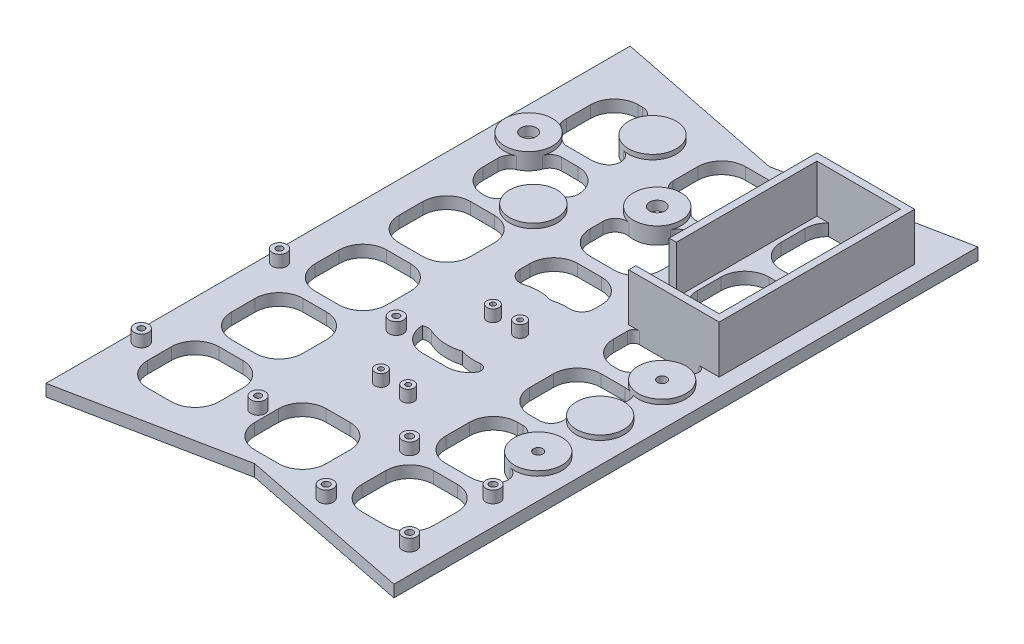
SolidWorks part; units mm, degrees
material "ABS"
ref_plane "Front Plane" through (0, 0, 0) normal (0, 0, 1) x (1, 0, 0)
ref_plane "Top Plane" through (0, 0, 0) normal (0, 1, 0) x (1, 0, 0)
ref_plane "Right Plane" through (0, 0, 0) normal (1, 0, 0) x (0, 0, -1)
ref_axis "X" through (-88.99, 0, 0) along (1, 0, 0)
ref_axis "Y" through (0, 55, 0) along (0, -1, 0)
ref_axis "Z" through (0, 0, -88.99) along (0, 0, 1)
sketch "Sketch1" plane through (0, 0, 0) normal (0, 1, 0) x (1, 0, 0)
  line L0 (-75, 125) -> (0, 110) construction
  line L1 (-75, 125) -> (75, 125) construction
  line L2 (-75, 125) -> (-75, -125) construction
  line L3 (-75, -125) -> (75, -125) construction
  line L4 (75, 125) -> (75, -125) construction
  line L5 (-75, 125) -> (75, -125) construction
  line L6 (-75, -125) -> (75, 125) construction
  line L7 (0, 110) -> (75, 125) construction
  line L8 (-75, 0) -> (75, 0) construction
  line L9 (-75, -125) -> (0, -110) construction
  line L10 (0, -110) -> (75, -125) construction
  line L11 (-73, 122.5604) -> (-73, -122.5604)
  line L12 (-73, -122.5604) -> (0, -107.9604)
  line L13 (0, -107.9604) -> (73, -122.5604)
  line L14 (73, 122.5604) -> (73, -122.5604)
  line L15 (0, 107.9604) -> (73, 122.5604)
  line L16 (-73, 122.5604) -> (0, 107.9604)
  point P0 (0, 0)
  dimension "D1" = 250
  dimension "D2" = 150
  dimension "D3" = 15
  dimension "D4" = 2
extrude "Boss-Extrude1" add sketch "Sketch1" along normal blind 2
sketch "Sketch2" plane through (0, 2, 0) normal (0, 1, 0) x (1, 0, 0)
  line L0 (-73, 122.5604) -> (-73, -122.5604) construction
  line L1 (-50, -102.9604) -> (-40, -102.9604)
  line L2 (-60, -92.9604) -> (-60, -82.9604)
  line L3 (-50, -72.9604) -> (-40, -72.9604)
  line L4 (-30, -92.9604) -> (-30, -82.9604)
  line L5 (-15, -92.9604) -> (-15, -82.9604)
  line L6 (-5, -102.9604) -> (5, -102.9604)
  line L7 (15, -92.9604) -> (15, -82.9604)
  line L8 (-5, -72.9604) -> (5, -72.9604)
  line L9 (30, -92.9604) -> (30, -82.9604)
  line L10 (40, -102.9604) -> (50, -102.9604)
  line L11 (60, -92.9604) -> (60, -82.9604)
  line L12 (40, -72.9604) -> (50, -72.9604)
  line L73 (-60, -57.7762) -> (-60, -47.7762)
  line L74 (-50, -67.7762) -> (-40, -67.7762)
  line L75 (-30, -57.7762) -> (-30, -47.7762)
  line L76 (-50, -37.7762) -> (-40, -37.7762)
  line L77 (-15, -57.7762) -> (-15, -47.7762)
  line L78 (-5, -37.7762) -> (5, -37.7762)
  line L79 (15, -57.7762) -> (15, -47.7762)
  line L80 (-5, -67.7762) -> (5, -67.7762)
  line L81 (30, -57.7762) -> (30, -47.7762)
  line L82 (40, -37.7762) -> (50, -37.7762)
  line L83 (60, -57.7762) -> (60, -47.7762)
  line L84 (40, -67.7762) -> (50, -67.7762)
  line L85 (-60, -22.5921) -> (-60, -12.5921)
  line L86 (-50, -32.5921) -> (-40, -32.5921)
  line L87 (-30, -22.5921) -> (-30, -12.5921)
  line L88 (-50, -2.5921) -> (-40, -2.5921)
  line L89 (-15, -22.5921) -> (-15, -12.5921)
  line L90 (-5, -2.5921) -> (5, -2.5921)
  line L91 (15, -22.5921) -> (15, -12.5921)
  line L92 (-5, -32.5921) -> (5, -32.5921)
  line L93 (30, -22.5921) -> (30, -12.5921)
  line L94 (40, -2.5921) -> (50, -2.5921)
  line L95 (60, -22.5921) -> (60, -12.5921)
  line L96 (40, -32.5921) -> (50, -32.5921)
  line L97 (-60, 12.5921) -> (-60, 22.5921)
  line L98 (-50, 2.5921) -> (-40, 2.5921)
  line L99 (-30, 12.5921) -> (-30, 22.5921)
  line L100 (-50, 32.5921) -> (-40, 32.5921)
  line L101 (-15, 12.5921) -> (-15, 22.5921)
  line L102 (-5, 32.5921) -> (5, 32.5921)
  line L103 (15, 12.5921) -> (15, 22.5921)
  line L104 (-5, 2.5921) -> (5, 2.5921)
  line L105 (30, 12.5921) -> (30, 22.5921)
  line L106 (40, 32.5921) -> (50, 32.5921)
  line L107 (60, 12.5921) -> (60, 22.5921)
  line L108 (40, 2.5921) -> (50, 2.5921)
  line L109 (-60, 47.7762) -> (-60, 57.7762)
  line L110 (-50, 37.7762) -> (-40, 37.7762)
  line L111 (-30, 47.7762) -> (-30, 57.7762)
  line L112 (-50, 67.7762) -> (-40, 67.7762)
  line L113 (-15, 47.7762) -> (-15, 57.7762)
  line L114 (-5, 67.7762) -> (5, 67.7762)
  line L115 (15, 47.7762) -> (15, 57.7762)
  line L116 (-5, 37.7762) -> (5, 37.7762)
  line L117 (30, 47.7762) -> (30, 57.7762)
  line L118 (40, 67.7762) -> (50, 67.7762)
  line L119 (60, 47.7762) -> (60, 57.7762)
  line L120 (40, 37.7762) -> (50, 37.7762)
  line L121 (-60, 82.9604) -> (-60, 92.9604)
  line L122 (-50, 72.9604) -> (-40, 72.9604)
  line L123 (-30, 82.9604) -> (-30, 92.9604)
  line L124 (-50, 102.9604) -> (-40, 102.9604)
  line L125 (-15, 82.9604) -> (-15, 92.9604)
  line L126 (-5, 102.9604) -> (5, 102.9604)
  line L127 (15, 82.9604) -> (15, 92.9604)
  line L128 (-5, 72.9604) -> (5, 72.9604)
  line L129 (30, 82.9604) -> (30, 92.9604)
  line L130 (40, 102.9604) -> (50, 102.9604)
  line L131 (60, 82.9604) -> (60, 92.9604)
  line L132 (40, 72.9604) -> (50, 72.9604)
  arc A0 (-60, -92.9604) -> (-50, -102.9604) centre (-50, -92.9604) ccw
  arc A1 (-40, -102.9604) -> (-30, -92.9604) centre (-40, -92.9604) ccw
  arc A2 (-30, -82.9604) -> (-40, -72.9604) centre (-40, -82.9604) ccw
  arc A3 (-50, -72.9604) -> (-60, -82.9604) centre (-50, -82.9604) ccw
  arc A4 (60, -82.9604) -> (50, -72.9604) centre (50, -82.9604) ccw
  arc A5 (50, -102.9604) -> (60, -92.9604) centre (50, -92.9604) ccw
  arc A6 (40, -102.9604) -> (30, -92.9604) centre (40, -92.9604) cw
  arc A7 (30, -82.9604) -> (40, -72.9604) centre (40, -82.9604) cw
  arc A8 (-15, -82.9604) -> (-5, -72.9604) centre (-5, -82.9604) cw
  arc A9 (-15, -92.9604) -> (-5, -102.9604) centre (-5, -92.9604) ccw
  arc A10 (15, -92.9604) -> (5, -102.9604) centre (5, -92.9604) cw
  arc A11 (15, -82.9604) -> (5, -72.9604) centre (5, -82.9604) ccw
  arc A12 (-50, -37.7762) -> (-60, -47.7762) centre (-50, -47.7762) ccw
  arc A13 (-60, -57.7762) -> (-50, -67.7762) centre (-50, -57.7762) ccw
  arc A14 (-40, -67.7762) -> (-30, -57.7762) centre (-40, -57.7762) ccw
  arc A15 (-30, -47.7762) -> (-40, -37.7762) centre (-40, -47.7762) ccw
  arc A16 (-15, -57.7762) -> (-5, -67.7762) centre (-5, -57.7762) ccw
  arc A17 (-15, -47.7762) -> (-5, -37.7762) centre (-5, -47.7762) cw
  arc A18 (15, -47.7762) -> (5, -37.7762) centre (5, -47.7762) ccw
  arc A19 (15, -57.7762) -> (5, -67.7762) centre (5, -57.7762) cw
  arc A20 (30, -47.7762) -> (40, -37.7762) centre (40, -47.7762) cw
  arc A21 (40, -67.7762) -> (30, -57.7762) centre (40, -57.7762) cw
  arc A22 (60, -47.7762) -> (50, -37.7762) centre (50, -47.7762) ccw
  arc A23 (50, -67.7762) -> (60, -57.7762) centre (50, -57.7762) ccw
  arc A24 (-50, -2.5921) -> (-60, -12.5921) centre (-50, -12.5921) ccw
  arc A25 (-60, -22.5921) -> (-50, -32.5921) centre (-50, -22.5921) ccw
  arc A26 (-40, -32.5921) -> (-30, -22.5921) centre (-40, -22.5921) ccw
  arc A27 (-30, -12.5921) -> (-40, -2.5921) centre (-40, -12.5921) ccw
  arc A28 (-15, -22.5921) -> (-5, -32.5921) centre (-5, -22.5921) ccw
  arc A29 (-15, -12.5921) -> (-5, -2.5921) centre (-5, -12.5921) cw
  arc A30 (15, -12.5921) -> (5, -2.5921) centre (5, -12.5921) ccw
  arc A31 (15, -22.5921) -> (5, -32.5921) centre (5, -22.5921) cw
  arc A32 (30, -12.5921) -> (40, -2.5921) centre (40, -12.5921) cw
  arc A33 (40, -32.5921) -> (30, -22.5921) centre (40, -22.5921) cw
  arc A34 (60, -12.5921) -> (50, -2.5921) centre (50, -12.5921) ccw
  arc A35 (50, -32.5921) -> (60, -22.5921) centre (50, -22.5921) ccw
  arc A36 (-50, 32.5921) -> (-60, 22.5921) centre (-50, 22.5921) ccw
  arc A37 (-60, 12.5921) -> (-50, 2.5921) centre (-50, 12.5921) ccw
  arc A38 (-40, 2.5921) -> (-30, 12.5921) centre (-40, 12.5921) ccw
  arc A39 (-30, 22.5921) -> (-40, 32.5921) centre (-40, 22.5921) ccw
  arc A40 (-15, 12.5921) -> (-5, 2.5921) centre (-5, 12.5921) ccw
  arc A41 (-15, 22.5921) -> (-5, 32.5921) centre (-5, 22.5921) cw
  arc A42 (15, 22.5921) -> (5, 32.5921) centre (5, 22.5921) ccw
  arc A43 (15, 12.5921) -> (5, 2.5921) centre (5, 12.5921) cw
  arc A44 (30, 22.5921) -> (40, 32.5921) centre (40, 22.5921) cw
  arc A45 (40, 2.5921) -> (30, 12.5921) centre (40, 12.5921) cw
  arc A46 (60, 22.5921) -> (50, 32.5921) centre (50, 22.5921) ccw
  arc A47 (50, 2.5921) -> (60, 12.5921) centre (50, 12.5921) ccw
  arc A48 (-50, 67.7762) -> (-60, 57.7762) centre (-50, 57.7762) ccw
  arc A49 (-60, 47.7762) -> (-50, 37.7762) centre (-50, 47.7762) ccw
  arc A50 (-40, 37.7762) -> (-30, 47.7762) centre (-40, 47.7762) ccw
  arc A51 (-30, 57.7762) -> (-40, 67.7762) centre (-40, 57.7762) ccw
  arc A52 (-15, 47.7762) -> (-5, 37.7762) centre (-5, 47.7762) ccw
  arc A53 (-15, 57.7762) -> (-5, 67.7762) centre (-5, 57.7762) cw
  arc A54 (15, 57.7762) -> (5, 67.7762) centre (5, 57.7762) ccw
  arc A55 (15, 47.7762) -> (5, 37.7762) centre (5, 47.7762) cw
  arc A56 (30, 57.7762) -> (40, 67.7762) centre (40, 57.7762) cw
  arc A57 (40, 37.7762) -> (30, 47.7762) centre (40, 47.7762) cw
  arc A58 (60, 57.7762) -> (50, 67.7762) centre (50, 57.7762) ccw
  arc A59 (50, 37.7762) -> (60, 47.7762) centre (50, 47.7762) ccw
  arc A60 (-50, 102.9604) -> (-60, 92.9604) centre (-50, 92.9604) ccw
  arc A61 (-60, 82.9604) -> (-50, 72.9604) centre (-50, 82.9604) ccw
  arc A62 (-40, 72.9604) -> (-30, 82.9604) centre (-40, 82.9604) ccw
  arc A63 (-30, 92.9604) -> (-40, 102.9604) centre (-40, 92.9604) ccw
  arc A64 (-15, 82.9604) -> (-5, 72.9604) centre (-5, 82.9604) ccw
  arc A65 (-15, 92.9604) -> (-5, 102.9604) centre (-5, 92.9604) cw
  arc A66 (15, 92.9604) -> (5, 102.9604) centre (5, 92.9604) ccw
  arc A67 (15, 82.9604) -> (5, 72.9604) centre (5, 82.9604) cw
  arc A68 (30, 92.9604) -> (40, 102.9604) centre (40, 92.9604) cw
  arc A69 (40, 72.9604) -> (30, 82.9604) centre (40, 82.9604) cw
  arc A70 (60, 92.9604) -> (50, 102.9604) centre (50, 92.9604) ccw
  arc A71 (50, 72.9604) -> (60, 82.9604) centre (50, 82.9604) ccw
  point P81 (-30, -102.9604)
  point P84 (-30, -72.9604)
  point P87 (-60, -72.9604)
  dimension "D9" = 10
  dimension "D7" = 10
  dimension "D1" = 30
  dimension "D2" = 30
  dimension "D3" = 13
  dimension "D4" = 5
  dimension "D6" = 15
  dimension "D8" = 6
  dimension "D10" = 5
  dimension "D5" = 3
extrude "Cut-Extrude1" cut sketch "Sketch2" against normal through all
sketch "Sketch3" plane through (0, 2, 0) normal (0, 1, 0) x (1, 0, 0)
  line L1 (-73, 122.5604) -> (-73, -122.5604) construction
  circle A0 centre (-68, -29.5604) radius 3
  circle A1 centre (-19, -29.5604) radius 3
  circle A2 centre (-68, -87.5604) radius 3
  circle A3 centre (-19, -87.5604) radius 3
  dimension "D1" = 6
  dimension "D2" = 49
  dimension "D3" = 58
  dimension "D4" = 5
  dimension "D5" = 35
extrude "Boss-Extrude2" add sketch "Sketch3" along normal blind 5 and the other way through all
sketch "Sketch4" plane through (0, 7, 0) normal (0, 1, 0) x (1, 0, 0)
  circle A1 centre (-19, -87.5604) radius 1.35
  circle A2 centre (-68, -87.5604) radius 1.35
  circle A3 centre (-68, -29.5604) radius 1.35
  circle A4 centre (-19, -29.5604) radius 1.35
  dimension "D1" = 2.7
extrude "Cut-Extrude2" cut sketch "Sketch4" against normal through all
sketch "Sketch5" plane through (0, 2, 0) normal (0, 1, 0) x (1, 0, 0)
  line L0 (30, -87.9604) -> (60, -87.9604) construction
  line L1 (30, -82.9604) -> (30, -92.9604) construction
  line L2 (60, -92.9604) -> (60, -82.9604) construction
  circle A0 centre (27.5, -70.4604) radius 3
  circle A2 centre (62.5, -70.4604) radius 3
  circle A4 centre (62.5, -105.4604) radius 3
  circle A6 centre (27.5, -105.4604) radius 3
  circle A9 centre (45, -87.9604) radius 24.7487 construction
  dimension "D2" = 6
  dimension "D3" = 35
  dimension "D4" = 35
extrude "Boss-Extrude3" add sketch "Sketch5" along normal blind 5
sketch "Sketch6" plane through (0, 7, 0) normal (0, 1, 0) x (1, 0, 0)
  circle A0 centre (27.5, -70.4604) radius 1.5
  circle A1 centre (62.5, -70.4604) radius 1.5
  circle A2 centre (62.5, -105.4604) radius 1.5
  circle A3 centre (27.5, -105.4604) radius 1.5
  dimension "D1" = 3
extrude "Cut-Extrude3" cut sketch "Sketch6" against normal through all
sketch "Sketch7" plane through (0, 2, 0) normal (0, 1, 0) x (1, 0, 0)
  line L0 (73, -122.5604) -> (73, 122.5604) construction
  line L3 (57, 6) -> (57, -46) construction
  circle A0 centre (57, -46) radius 10
  circle A1 centre (57, 6) radius 10
  circle A2 centre (57, -20) radius 10
  point P6 (0, 0)
  point P7 (0, 0)
  dimension "D1" = 20
  dimension "D2" = 16
  dimension "D3" = 52
  dimension "D4" = 20
extrude "Boss-Extrude4" add sketch "Sketch7" along normal blind 2 and the other way through all
sketch "Sketch8" plane through (0, 4, 0) normal (0, 1, 0) x (1, 0, 0)
  circle A0 centre (57, 6) radius 1.95
  circle A1 centre (57, -46) radius 1.95
  dimension "D1" = 3.9
extrude "Cut-Extrude4" cut sketch "Sketch8" against normal through all
sketch "Sketch9" plane through (0, 2, 0) normal (0, 1, 0) x (1, 0, 0)
  line L0 (-73, 0) -> (73, 0) construction
  line L2 (-73, 122.5604) -> (-73, -122.5604) construction
  line L3 (73, -122.5604) -> (73, 122.5604) construction
  circle A0 centre (-3, -5) radius 2.5
  circle A1 centre (-3, -52) radius 2.5
  circle A2 centre (8.4, -52) radius 2.5
  circle A3 centre (8.4, -5) radius 2.5
  dimension "D1" = 5
  dimension "D4" = 70
  dimension "D2" = 11.4
  dimension "D3" = 47
  dimension "D5" = 5
extrude "Boss-Extrude5" add sketch "Sketch9" along normal blind 5
sketch "Sketch16" plane through (0, 2, 0) normal (0, -1, 0) x (1, 0, 0)
  line L0 (-5, 32.5921) -> (5, 32.5921) construction
  line L1 (-93.8107, 28.5) -> (150.737, 28.5) construction
  line L4 (-3, 52) -> (-3, 5) construction
  circle A0 centre (8.4, 52) radius 19.4079
  circle A1 centre (-3, 52) radius 19.4079
  circle A4 centre (-3, 52) radius 2.5 construction
  circle A5 centre (-3, 5) radius 2.5 construction
  circle A6 centre (-3, 52) radius 2.5 construction
  circle A7 centre (-3, 5) radius 2.5 construction
  circle A8 centre (8.4, 5) radius 19.4079
  circle A9 centre (-3, 5) radius 19.4079
  point P20 (-3, 28.5)
  circle M3 centre (8.4, 52) radius 2.5
extrude "Boss-Extrude10" add sketch "Sketch16" along normal up to surface (2 mm away) contours A0 A1 | A0 A1 M3 | M3 | A1 A0 | A9 | A8 region at (18.1683, 2, 52) region at (2.5462, 2, 52) region at (-12.7683, 2, 52) region at (8.4, 2, 52) up to face at (57, 0, -4.05)
sketch "Sketch10" plane through (0, 7, 0) normal (0, 1, 0) x (1, 0, 0)
  circle A0 centre (8.4, -5) radius 1.05
  circle A1 centre (8.4, -52) radius 1.05
  circle A2 centre (-3, -52) radius 1.05
  circle A3 centre (-3, -5) radius 1.05
  dimension "D1" = 2.1
extrude "Cut-Extrude5" cut sketch "Sketch10" against normal through all
sketch "Sketch11" plane through (0, 2, 0) normal (0, 1, 0) x (1, 0, 0)
  line L0 (-73, 122.5604) -> (-73, -122.5604) construction
  line L1 (-34, 92.9604) -> (-34, 42.9604) construction
  line L2 (-61, 67.9604) -> (-7, 67.9604) construction
  circle A3 centre (-7, 67.9604) radius 10
  circle A4 centre (-61, 67.9604) radius 10
  circle A5 centre (-34, 92.9604) radius 10
  circle A6 centre (-34, 42.9604) radius 10
  point P11 (-34, 67.9604)
  dimension "D1" = 20
  dimension "D2" = 54
  dimension "D3" = 40
  dimension "D4" = 12
  dimension "D5" = 50
extrude "Boss-Extrude6" add sketch "Sketch11" along normal blind 2 and the other way through all
sketch "Sketch12" plane through (0, 4, 0) normal (0, 1, 0) x (1, 0, 0)
  circle A0 centre (-61, 67.9604) radius 3.25
  circle A1 centre (-7, 67.9604) radius 3.25
  dimension "D1" = 6.5
extrude "Cut-Extrude6" cut sketch "Sketch12" against normal through all
sketch "Sketch13" plane through (0, 2, 0) normal (0, 1, 0) x (1, 0, 0)
  line L0 (28, 20.9604) -> (66, 20.9604)
  line L1 (66, 20.9604) -> (66, 102.9604)
  line L2 (66, 102.9604) -> (25, 102.9604)
  line L3 (25, 102.9604) -> (25, 40.9604)
  line L4 (25, 40.9604) -> (28, 40.9604)
  line L5 (28, 40.9604) -> (28, 99.9604)
  line L6 (28, 99.9604) -> (63, 99.9604)
  line L7 (63, 99.9604) -> (63, 23.9604)
  line L8 (63, 23.9604) -> (28, 23.9604)
  line L9 (28, 23.9604) -> (28, 20.9604)
  line L10 (73, -122.5604) -> (73, 122.5604) construction
  line L11 (50, 102.9604) -> (40, 102.9604) construction
  dimension "D1" = 62
  dimension "D2" = 3
  dimension "D3" = 3
  dimension "D4" = 3
  dimension "D5" = 3
  dimension "D6" = 35
  dimension "D7" = 76
  dimension "D9" = 7
extrude "Boss-Extrude7" add sketch "Sketch13" along normal blind 20 and the other way through all
fillet "Fillet2" radius 5 20 edges at (47.5986, 1, -2.5921) (51.2064, 1, 37.8493) (56.7216, 1, 29.9961) (59.7538, 1, 10.3866) (-30, 1, -52.1255) (-12.481, 1, -76.3245) (1.6603, 1, -72.9604) (-58.4629, 1, -77.6332) (-52.5371, 1, -73.2876) (-30, 1, -83.7952) (-37, 1, -102.4998) (2.9983, 1, -67.7762) (-14.3879, 1, -61.2211) (-42.5513, 1, -37.7762) (-59.9972, 1, -58.0108) (-51.0028, 1, -67.7258) (60, 1, 55.5394) (-14.7647, 1, -10.4356) (15, 1, -13.2512) (-15, 1, 20.2534)
fillet "Fillet3" radius 2.5 6 edges at (14.9777, 1, 23.2593) (60, 1, -15.5394) (30.0941, 1, -23.9604) (59.9059, 1, -23.9604) (30, 1, -20.9604) (60, 1, -20.9604)
sketch "Sketch15" plane through (0, 0, 0) normal (0, -1, 0) x (1, 0, 0)
  line L0 (0, 107.9604) -> (73, 122.5604) construction
  line L1 (-73, 122.5604) -> (0, 107.9604) construction
  line L2 (73, 122.5604) -> (73, -122.5604) construction
  line L3 (73, -122.5604) -> (0, -107.9604) construction
  line L4 (0, -107.9604) -> (-73, -122.5604) construction
  line L5 (-73, -122.5604) -> (-73, 122.5604) construction
  line L6 (0, 107.9604) -> (73, 122.5604)
  line L7 (-73, 122.5604) -> (0, 107.9604)
  line L8 (73, 122.5604) -> (73, -122.5604)
  line L9 (73, -122.5604) -> (0, -107.9604)
  line L10 (0, -107.9604) -> (-73, -122.5604)
  line L11 (-73, -122.5604) -> (-73, 122.5604)
  line L12 (0, 104.901) -> (70, 118.901)
  line L13 (70, 118.901) -> (70, -118.901)
  line L14 (70, -118.901) -> (0, -104.901)
  line L15 (0, -104.901) -> (-70, -118.901)
  line L16 (-70, -118.901) -> (-70, 118.901)
  line L17 (-70, 118.901) -> (0, 104.901)
  dimension "D1" = 3
extrude "Boss-Extrude9" add sketch "Sketch15" along normal blind 3
sketch "Sketch17" plane through (0, 0, 0) normal (0, -1, 0) x (1, 0, 0)
  line L0 (-49.8197, -72.9604) -> (-40, -72.9604) construction
  line L1 (-60, -92.9604) -> (-60, -82.9604) construction
  line L2 (-48.1421, -102.9604) -> (-50, -102.9604) construction
  line L3 (-49.8197, -72.9604) -> (-40, -72.9604)
  line L4 (-60, -92.9604) -> (-60, -82.9604)
  line L5 (-48.1421, -102.9604) -> (-50, -102.9604)
  line L6 (4.1803, -72.9604) -> (5, -72.9604) construction
  line L7 (15, -82.9604) -> (15, -92.9604) construction
  line L8 (5, -102.9604) -> (-5, -102.9604) construction
  line L9 (-15, -92.9604) -> (-15, -82.9604) construction
  line L10 (4.1803, -72.9604) -> (5, -72.9604)
  line L11 (15, -82.9604) -> (15, -92.9604)
  line L12 (5, -102.9604) -> (-5, -102.9604)
  line L13 (-15, -92.9604) -> (-15, -82.9604)
  line L14 (60, -82.9604) -> (60, -92.9604) construction
  line L16 (30, -92.9604) -> (30, -82.9604) construction
  line L17 (40, -72.9604) -> (50, -72.9604) construction
  line L18 (60, -82.9604) -> (60, -92.9604)
  line L20 (30, -92.9604) -> (30, -82.9604)
  line L21 (40, -72.9604) -> (50, -72.9604)
  line L22 (-5, -37.7762) -> (5, -37.7762) construction
  line L23 (-15, -53.2635) -> (-15, -47.7762) construction
  line L24 (15, -47.7762) -> (15, -57.7762) construction
  line L25 (-5, -37.7762) -> (5, -37.7762)
  line L26 (-15, -53.2635) -> (-15, -47.7762)
  line L27 (15, -47.7762) -> (15, -57.7762)
  line L28 (-50, -37.7762) -> (-48.9989, -37.7762) construction
  line L29 (-40, -67.7762) -> (-46.9243, -67.7762) construction
  line L30 (-60, -54.2127) -> (-60, -47.7762) construction
  line L31 (-50, -37.7762) -> (-48.9989, -37.7762)
  line L32 (-40, -67.7762) -> (-46.9243, -67.7762)
  line L33 (-60, -54.2127) -> (-60, -47.7762)
  line L36 (60, -47.7762) -> (60, -57.7762) construction
  line L37 (50, -67.7762) -> (40, -67.7762) construction
  line L38 (30, -57.7762) -> (30, -47.7762) construction
  line L39 (40, -37.7762) -> (50, -37.7762) construction
  line L42 (60, -47.7762) -> (60, -57.7762)
  line L43 (50, -67.7762) -> (40, -67.7762)
  line L44 (30, -57.7762) -> (30, -47.7762)
  line L45 (40, -37.7762) -> (50, -37.7762)
  line L54 (-5, 32.5921) -> (5, 32.5921) construction
  line L58 (-5, 32.5921) -> (5, 32.5921)
  line L62 (-30, -12.5921) -> (-30, -22.5921) construction
  line L63 (-40, -32.5921) -> (-50, -32.5921) construction
  line L64 (-60, -22.5921) -> (-60, -12.5921) construction
  line L65 (-50, -2.5921) -> (-40, -2.5921) construction
  line L66 (15, -19.3554) -> (15, -22.5921) construction
  line L67 (-15, -22.5921) -> (-15, -18.3826) construction
  line L68 (5, -32.5921) -> (-5, -32.5921) construction
  line L69 (-30, -12.5921) -> (-30, -22.5921)
  line L70 (-40, -32.5921) -> (-50, -32.5921)
  line L71 (-60, -22.5921) -> (-60, -12.5921)
  line L72 (-50, -2.5921) -> (-40, -2.5921)
  line L73 (15, -19.3554) -> (15, -22.5921)
  line L74 (-15, -22.5921) -> (-15, -18.3826)
  line L75 (5, -32.5921) -> (-5, -32.5921)
  line L76 (-30, 22.5921) -> (-30, 12.5921) construction
  line L77 (-40, 2.5921) -> (-50, 2.5921) construction
  line L78 (-60, 12.5921) -> (-60, 22.5921) construction
  line L79 (-50, 32.5921) -> (-40, 32.5921) construction
  line L80 (-30, 22.5921) -> (-30, 12.5921)
  line L81 (-40, 2.5921) -> (-50, 2.5921)
  line L82 (-60, 12.5921) -> (-60, 22.5921)
  line L83 (-50, 32.5921) -> (-40, 32.5921)
  line L90 (-30, 57.7762) -> (-30, 47.7762) construction
  line L91 (-40, 37.7762) -> (-50, 37.7762) construction
  line L92 (-60, 47.7762) -> (-60, 57.7762) construction
  line L93 (-50, 67.7762) -> (-40, 67.7762) construction
  line L94 (-30, 57.7762) -> (-30, 47.7762)
  line L95 (-40, 37.7762) -> (-50, 37.7762)
  line L96 (-60, 47.7762) -> (-60, 57.7762)
  line L97 (-50, 67.7762) -> (-40, 67.7762)
  line L98 (-30, 92.9604) -> (-30, 82.9604) construction
  line L99 (-40, 72.9604) -> (-50, 72.9604) construction
  line L100 (-60, 82.9604) -> (-60, 92.9604) construction
  line L101 (-50, 102.9604) -> (-40, 102.9604) construction
  line L102 (-30, 92.9604) -> (-30, 82.9604)
  line L103 (-40, 72.9604) -> (-50, 72.9604)
  line L104 (-60, 82.9604) -> (-60, 92.9604)
  line L105 (-50, 102.9604) -> (-40, 102.9604)
  line L106 (40, 32.5921) -> (44.0632, 32.5921) construction
  line L107 (30, 12.5921) -> (30, 22.5921) construction
  line L108 (50, 2.5921) -> (40, 2.5921) construction
  line L109 (50, -32.5921) -> (40, -32.5921) construction
  line L110 (56.4254, -23.9604) -> (33.5746, -23.9604) construction
  line L111 (32.5, -20.9604) -> (57.5, -20.9604) construction
  line L112 (30, -18.4604) -> (30, -12.5921) construction
  line L113 (40, -2.5921) -> (42.0847, -2.5921) construction
  line L114 (40, 32.5921) -> (44.0632, 32.5921)
  line L115 (30, 12.5921) -> (30, 22.5921)
  line L116 (50, 2.5921) -> (40, 2.5921)
  line L117 (50, -32.5921) -> (40, -32.5921)
  line L118 (56.4254, -23.9604) -> (33.5746, -23.9604)
  line L119 (32.5, -20.9604) -> (57.5, -20.9604)
  line L120 (30, -18.4604) -> (30, -12.5921)
  line L121 (40, -2.5921) -> (42.0847, -2.5921)
  line L122 (15, 92.9604) -> (15, 82.9604) construction
  line L123 (-5, 102.9604) -> (5, 102.9604) construction
  line L124 (-15, 82.9604) -> (-15, 92.9604) construction
  line L125 (5, 72.9604) -> (-5, 72.9604) construction
  line L126 (60, 92.9604) -> (60, 82.9604) construction
  line L127 (50, 72.9604) -> (40, 72.9604) construction
  line L128 (30, 82.9604) -> (30, 92.9604) construction
  line L129 (40, 102.9604) -> (50, 102.9604) construction
  line L130 (30, 47.7762) -> (30, 57.7762) construction
  line L131 (42.3505, 37.7762) -> (40, 37.7762) construction
  line L132 (40, 67.7762) -> (50, 67.7762) construction
  line L133 (15, 92.9604) -> (15, 82.9604)
  line L134 (-5, 102.9604) -> (5, 102.9604)
  line L135 (-15, 82.9604) -> (-15, 92.9604)
  line L136 (5, 72.9604) -> (-5, 72.9604)
  line L137 (60, 92.9604) -> (60, 82.9604)
  line L138 (50, 72.9604) -> (40, 72.9604)
  line L139 (30, 82.9604) -> (30, 92.9604)
  line L140 (40, 102.9604) -> (50, 102.9604)
  line L141 (30, 47.7762) -> (30, 57.7762)
  line L142 (42.3505, 37.7762) -> (40, 37.7762)
  line L143 (40, 67.7762) -> (50, 67.7762)
  line L144 (32.8586, -99.9604) -> (57.1414, -99.9604) construction
  line L145 (32.8586, -99.9604) -> (57.1414, -99.9604)
  line L146 (4.1803, -70.9604) -> (5, -70.9604)
  line L147 (17, -82.9604) -> (17, -92.9604)
  line L148 (5, -104.9604) -> (-5, -104.9604)
  line L149 (-17, -92.9604) -> (-17, -82.9604)
  line L150 (62, -82.9604) -> (62, -92.9604)
  line L151 (40, -70.9604) -> (50, -70.9604)
  line L152 (28, -92.9604) -> (28, -82.9604)
  line L153 (32.0627, -101.9604) -> (57.9373, -101.9604)
  line L154 (40, -35.7762) -> (50, -35.7762)
  line L155 (28, -57.7762) -> (28, -47.7762)
  line L156 (50, -69.7762) -> (40, -69.7762)
  line L157 (62, -47.7762) -> (62, -57.7762)
  line L158 (-5, -35.7762) -> (5, -35.7762)
  line L159 (-17, -53.2635) -> (-17, -47.7762)
  line L160 (17, -47.7762) -> (17, -57.7762)
  line L161 (-50, -35.7762) -> (-48.9989, -35.7762)
  line L162 (-40, -69.7762) -> (-46.9243, -69.7762)
  line L163 (-62, -54.2127) -> (-62, -47.7762)
  line L164 (-49.8197, -70.9604) -> (-40, -70.9604)
  line L165 (-62, -92.9604) -> (-62, -82.9604)
  line L166 (-48.1421, -104.9604) -> (-50, -104.9604)
  line L167 (40, -0.5921) -> (42.0847, -0.5921)
  line L168 (28, -18.4604) -> (28, -12.5921)
  line L171 (50, -34.5921) -> (40, -34.5921)
  line L172 (-17, -22.5921) -> (-17, -18.3826)
  line L173 (5, -34.5921) -> (-5, -34.5921)
  line L174 (17, -19.3554) -> (17, -22.5921)
  line L175 (-50, -0.5921) -> (-40, -0.5921)
  line L176 (-62, -22.5921) -> (-62, -12.5921)
  line L177 (-40, -34.5921) -> (-50, -34.5921)
  line L178 (-28, -12.5921) -> (-28, -22.5921)
  line L179 (-50, 34.5921) -> (-40, 34.5921)
  line L180 (-62, 12.5921) -> (-62, 22.5921)
  line L181 (-40, 0.5921) -> (-50, 0.5921)
  line L182 (-28, 22.5921) -> (-28, 12.5921)
  line L183 (40, 34.5921) -> (44.0632, 34.5921)
  line L184 (28, 12.5921) -> (28, 22.5921)
  line L185 (50, 0.5921) -> (40, 0.5921)
  line L186 (-5, 34.5921) -> (5, 34.5921)
  line L187 (32.5, -22.9604) -> (57.5, -22.9604) construction
  line L188 (56.4254, -21.9604) -> (33.5746, -21.9604) construction
  line L189 (17, 92.9604) -> (17, 82.9604)
  line L190 (5, 70.9604) -> (-5, 70.9604)
  line L191 (-17, 82.9604) -> (-17, 92.9604)
  line L192 (-5, 104.9604) -> (5, 104.9604)
  line L193 (-50, 104.9604) -> (-40, 104.9604)
  line L194 (-62, 82.9604) -> (-62, 92.9604)
  line L195 (-40, 70.9604) -> (-50, 70.9604)
  line L196 (-28, 92.9604) -> (-28, 82.9604)
  line L197 (-50, 69.7762) -> (-40, 69.7762)
  line L198 (-62, 47.7762) -> (-62, 57.7762)
  line L199 (-40, 35.7762) -> (-50, 35.7762)
  line L200 (-28, 57.7762) -> (-28, 47.7762)
  line L201 (28, 47.7762) -> (28, 57.7762)
  line L202 (40, 69.7762) -> (50, 69.7762)
  line L203 (42.3505, 35.7762) -> (40, 35.7762)
  line L204 (62, 92.9604) -> (62, 82.9604)
  line L205 (50, 70.9604) -> (40, 70.9604)
  line L206 (28, 82.9604) -> (28, 92.9604)
  line L207 (40, 104.9604) -> (50, 104.9604)
  arc A0 (-48.1421, -102.9604) -> (-43.4281, -96.2937) centre (-48.1421, -97.9604) ccw construction
  arc A1 (-36.5518, -83.2914) -> (-43.4281, -96.2937) centre (-34, -92.9604) ccw construction
  arc A2 (-36.5518, -83.2914) -> (-35.6553, -73.9535) centre (-37.8276, -78.457) ccw construction
  arc A3 (-35.6553, -73.9535) -> (-40, -72.9604) centre (-40, -82.9604) ccw construction
  arc A4 (-49.8197, -72.9604) -> (-53.5464, -74.6271) centre (-49.8197, -77.9604) ccw construction
  arc A5 (-56.8794, -77.072) -> (-53.5464, -74.6271) centre (-61, -67.9604) ccw construction
  arc A6 (-56.8794, -77.072) -> (-59.6383, -80.2951) centre (-54.8191, -81.6278) ccw construction
  arc A7 (-59.6383, -80.2951) -> (-60, -82.9604) centre (-50, -82.9604) ccw construction
  arc A8 (-60, -92.9604) -> (-50, -102.9604) centre (-50, -92.9604) ccw construction
  arc A9 (-48.1421, -102.9604) -> (-43.4281, -96.2937) centre (-48.1421, -97.9604) ccw
  arc A10 (-36.5518, -83.2914) -> (-43.4281, -96.2937) centre (-34, -92.9604) ccw
  arc A11 (-36.5518, -83.2914) -> (-35.6553, -73.9535) centre (-37.8276, -78.457) ccw
  arc A12 (-35.6553, -73.9535) -> (-40, -72.9604) centre (-40, -82.9604) ccw
  arc A13 (-49.8197, -72.9604) -> (-53.5464, -74.6271) centre (-49.8197, -77.9604) ccw
  arc A14 (-56.8794, -77.072) -> (-53.5464, -74.6271) centre (-61, -67.9604) ccw
  arc A15 (-56.8794, -77.072) -> (-59.6383, -80.2951) centre (-54.8191, -81.6278) ccw
  arc A16 (-59.6383, -80.2951) -> (-60, -82.9604) centre (-50, -82.9604) ccw
  arc A17 (-60, -92.9604) -> (-50, -102.9604) centre (-50, -92.9604) ccw
  arc A18 (-8.9939, -77.7596) -> (0.4536, -74.6271) centre (-7, -67.9604) ccw construction
  arc A19 (4.1803, -72.9604) -> (0.4536, -74.6271) centre (4.1803, -77.9604) ccw construction
  arc A20 (15, -82.9604) -> (5, -72.9604) centre (5, -82.9604) ccw construction
  arc A21 (5, -102.9604) -> (15, -92.9604) centre (5, -92.9604) ccw construction
  arc A22 (-15, -92.9604) -> (-5, -102.9604) centre (-5, -92.9604) ccw construction
  arc A23 (-14.9818, -82.358) -> (-15, -82.9604) centre (-5, -82.9604) ccw construction
  arc A24 (-8.9939, -77.7596) -> (-14.9818, -82.358) centre (-9.9909, -82.6592) ccw construction
  arc A25 (-8.9939, -77.7596) -> (0.4536, -74.6271) centre (-7, -67.9604) ccw
  arc A26 (4.1803, -72.9604) -> (0.4536, -74.6271) centre (4.1803, -77.9604) ccw
  arc A27 (15, -82.9604) -> (5, -72.9604) centre (5, -82.9604) ccw
  arc A28 (5, -102.9604) -> (15, -92.9604) centre (5, -92.9604) ccw
  arc A29 (-15, -92.9604) -> (-5, -102.9604) centre (-5, -92.9604) ccw
  arc A30 (-14.9818, -82.358) -> (-15, -82.9604) centre (-5, -82.9604) ccw
  arc A31 (-8.9939, -77.7596) -> (-14.9818, -82.358) centre (-9.9909, -82.6592) ccw
  arc A32 (60, -82.9604) -> (50, -72.9604) centre (50, -82.9604) ccw construction
  arc A33 (57.1414, -99.9604) -> (60, -92.9604) centre (50, -92.9604) ccw construction
  arc A34 (30, -92.9604) -> (32.8586, -99.9604) centre (40, -92.9604) ccw construction
  arc A35 (40, -72.9604) -> (30, -82.9604) centre (40, -82.9604) ccw construction
  arc A36 (60, -82.9604) -> (50, -72.9604) centre (50, -82.9604) ccw
  arc A37 (57.1414, -99.9604) -> (60, -92.9604) centre (50, -92.9604) ccw
  arc A38 (30, -92.9604) -> (32.8586, -99.9604) centre (40, -92.9604) ccw
  arc A39 (40, -72.9604) -> (30, -82.9604) centre (40, -82.9604) ccw
  arc A40 (15, -47.7762) -> (5, -37.7762) centre (5, -47.7762) ccw construction
  arc A41 (-5, -37.7762) -> (-15, -47.7762) centre (-5, -47.7762) ccw construction
  arc A42 (-15, -53.2635) -> (-9, -58.1624) centre (-10, -53.2635) ccw construction
  arc A43 (8.8546, -67.0035) -> (15, -57.7762) centre (5, -57.7762) ccw construction
  arc A44 (2.2849, -64.2467) -> (8.8546, -67.0035) centre (6.9273, -62.3899) ccw construction
  arc A45 (2.2849, -64.2467) -> (-9, -58.1624) centre (-7, -67.9604) ccw construction
  arc A46 (15, -47.7762) -> (5, -37.7762) centre (5, -47.7762) ccw
  arc A47 (-5, -37.7762) -> (-15, -47.7762) centre (-5, -47.7762) ccw
  arc A48 (-15, -53.2635) -> (-9, -58.1624) centre (-10, -53.2635) ccw
  arc A49 (8.8546, -67.0035) -> (15, -57.7762) centre (5, -57.7762) ccw
  arc A50 (2.2849, -64.2467) -> (8.8546, -67.0035) centre (6.9273, -62.3899) ccw
  arc A51 (2.2849, -64.2467) -> (-9, -58.1624) centre (-7, -67.9604) ccw
  arc A52 (-50, -37.7762) -> (-60, -47.7762) centre (-50, -47.7762) ccw construction
  arc A53 (-43.9992, -42.8376) -> (-48.9989, -37.7762) centre (-48.9989, -42.7762) ccw construction
  arc A54 (-43.9992, -42.8376) -> (-34.6682, -52.938) centre (-34, -42.9604) ccw construction
  arc A55 (-30.0045, -58.0775) -> (-34.6682, -52.938) centre (-35.0023, -57.9269) ccw construction
  arc A56 (-40, -67.7762) -> (-30.0045, -58.0775) centre (-40, -57.7762) ccw construction
  arc A57 (-51.6162, -64.5043) -> (-46.9243, -67.7762) centre (-46.9243, -62.7762) ccw construction
  arc A58 (-51.6162, -64.5043) -> (-57, -58.7952) centre (-61, -67.9604) ccw construction
  arc A59 (-60, -54.2127) -> (-57, -58.7952) centre (-55, -54.2127) ccw construction
  arc A60 (-50, -37.7762) -> (-60, -47.7762) centre (-50, -47.7762) ccw
  arc A61 (-43.9992, -42.8376) -> (-48.9989, -37.7762) centre (-48.9989, -42.7762) ccw
  arc A62 (-43.9992, -42.8376) -> (-34.6682, -52.938) centre (-34, -42.9604) ccw
  arc A63 (-30.0045, -58.0775) -> (-34.6682, -52.938) centre (-35.0023, -57.9269) ccw
  arc A64 (-40, -67.7762) -> (-30.0045, -58.0775) centre (-40, -57.7762) ccw
  arc A65 (-51.6162, -64.5043) -> (-46.9243, -67.7762) centre (-46.9243, -62.7762) ccw
  arc A66 (-51.6162, -64.5043) -> (-57, -58.7952) centre (-61, -67.9604) ccw
  arc A67 (-60, -54.2127) -> (-57, -58.7952) centre (-55, -54.2127) ccw
  arc A72 (60, -47.7762) -> (50, -37.7762) centre (50, -47.7762) ccw construction
  arc A73 (50, -67.7762) -> (60, -57.7762) centre (50, -57.7762) ccw construction
  arc A74 (30, -57.7762) -> (40, -67.7762) centre (40, -57.7762) ccw construction
  arc A75 (40, -37.7762) -> (30, -47.7762) centre (40, -47.7762) ccw construction
  arc A80 (60, -47.7762) -> (50, -37.7762) centre (50, -47.7762) ccw
  arc A81 (50, -67.7762) -> (60, -57.7762) centre (50, -57.7762) ccw
  arc A82 (30, -57.7762) -> (40, -67.7762) centre (40, -57.7762) ccw
  arc A83 (40, -37.7762) -> (30, -47.7762) centre (40, -47.7762) ccw
  arc A96 (10.9351, 24.2416) -> (13.3489, 28.0963) centre (11.2617, 26.7202) ccw construction
  arc A97 (13.3489, 28.0963) -> (5, 32.5921) centre (5, 22.5921) ccw construction
  arc A98 (-5, 32.5921) -> (-15, 22.5921) centre (-5, 22.5921) ccw construction
  arc A99 (-15, 22.5921) -> (-11.0339, 22.667) centre (-13.1037, 27.2185) ccw construction
  arc A100 (10.9351, 24.2416) -> (2.7, 23.552) centre (8.4, 5) ccw construction
  arc A101 (2.7, 23.552) -> (-11.0339, 22.667) centre (-3, 5) ccw construction
  arc A107 (10.9351, 24.2416) -> (13.3489, 28.0963) centre (11.2617, 26.7202) ccw
  arc A108 (13.3489, 28.0963) -> (5, 32.5921) centre (5, 22.5921) ccw
  arc A109 (-5, 32.5921) -> (-15, 22.5921) centre (-5, 22.5921) ccw
  arc A110 (-15, 22.5921) -> (-11.0339, 22.667) centre (-13.1037, 27.2185) ccw
  arc A111 (10.9351, 24.2416) -> (2.7, 23.552) centre (8.4, 5) ccw
  arc A112 (2.7, 23.552) -> (-11.0339, 22.667) centre (-3, 5) ccw
  arc A118 (-30, -12.5921) -> (-40, -2.5921) centre (-40, -12.5921) ccw construction
  arc A119 (-40, -32.5921) -> (-30, -22.5921) centre (-40, -22.5921) ccw construction
  arc A120 (-60, -22.5921) -> (-50, -32.5921) centre (-50, -22.5921) ccw construction
  arc A121 (-50, -2.5921) -> (-60, -12.5921) centre (-50, -12.5921) ccw construction
  arc A122 (15, -19.3554) -> (9.6722, -14.3662) centre (10, -19.3554) ccw construction
  arc A123 (5, -32.5921) -> (15, -22.5921) centre (5, -22.5921) ccw construction
  arc A124 (-15, -22.5921) -> (-5, -32.5921) centre (-5, -22.5921) ccw construction
  arc A125 (-8.566, -13.5926) -> (-15, -18.3826) centre (-10, -18.3826) ccw construction
  arc A126 (2.7, -13.552) -> (9.6722, -14.3662) centre (8.4, 5) ccw construction
  arc A127 (-8.566, -13.5926) -> (2.7, -13.552) centre (-3, 5) ccw construction
  arc A128 (-30, -12.5921) -> (-40, -2.5921) centre (-40, -12.5921) ccw
  arc A129 (-40, -32.5921) -> (-30, -22.5921) centre (-40, -22.5921) ccw
  arc A130 (-60, -22.5921) -> (-50, -32.5921) centre (-50, -22.5921) ccw
  arc A131 (-50, -2.5921) -> (-60, -12.5921) centre (-50, -12.5921) ccw
  arc A132 (15, -19.3554) -> (9.6722, -14.3662) centre (10, -19.3554) ccw
  arc A133 (5, -32.5921) -> (15, -22.5921) centre (5, -22.5921) ccw
  arc A134 (-15, -22.5921) -> (-5, -32.5921) centre (-5, -22.5921) ccw
  arc A135 (-8.566, -13.5926) -> (-15, -18.3826) centre (-10, -18.3826) ccw
  arc A136 (2.7, -13.552) -> (9.6722, -14.3662) centre (8.4, 5) ccw
  arc A137 (-8.566, -13.5926) -> (2.7, -13.552) centre (-3, 5) ccw
  arc A138 (-30, 22.5921) -> (-40, 32.5921) centre (-40, 22.5921) ccw construction
  arc A139 (-40, 2.5921) -> (-30, 12.5921) centre (-40, 12.5921) ccw construction
  arc A140 (-60, 12.5921) -> (-50, 2.5921) centre (-50, 12.5921) ccw construction
  arc A141 (-50, 32.5921) -> (-60, 22.5921) centre (-50, 22.5921) ccw construction
  arc A142 (-30, 22.5921) -> (-40, 32.5921) centre (-40, 22.5921) ccw
  arc A143 (-40, 2.5921) -> (-30, 12.5921) centre (-40, 12.5921) ccw
  arc A144 (-60, 12.5921) -> (-50, 2.5921) centre (-50, 12.5921) ccw
  arc A145 (-50, 32.5921) -> (-60, 22.5921) centre (-50, 22.5921) ccw
  arc A158 (-30, 57.7762) -> (-40, 67.7762) centre (-40, 57.7762) ccw construction
  arc A159 (-40, 37.7762) -> (-30, 47.7762) centre (-40, 47.7762) ccw construction
  arc A160 (-60, 47.7762) -> (-50, 37.7762) centre (-50, 47.7762) ccw construction
  arc A161 (-50, 67.7762) -> (-60, 57.7762) centre (-50, 57.7762) ccw construction
  arc A162 (-30, 57.7762) -> (-40, 67.7762) centre (-40, 57.7762) ccw
  arc A163 (-40, 37.7762) -> (-30, 47.7762) centre (-40, 47.7762) ccw
  arc A164 (-60, 47.7762) -> (-50, 37.7762) centre (-50, 47.7762) ccw
  arc A165 (-50, 67.7762) -> (-60, 57.7762) centre (-50, 57.7762) ccw
  arc A166 (-30, 92.9604) -> (-40, 102.9604) centre (-40, 92.9604) ccw construction
  arc A167 (-40, 72.9604) -> (-30, 82.9604) centre (-40, 82.9604) ccw construction
  arc A168 (-60, 82.9604) -> (-50, 72.9604) centre (-50, 82.9604) ccw construction
  arc A169 (-50, 102.9604) -> (-60, 92.9604) centre (-50, 92.9604) ccw construction
  arc A170 (-30, 92.9604) -> (-40, 102.9604) centre (-40, 92.9604) ccw
  arc A171 (-40, 72.9604) -> (-30, 82.9604) centre (-40, 82.9604) ccw
  arc A172 (-60, 82.9604) -> (-50, 72.9604) centre (-50, 82.9604) ccw
  arc A173 (-50, 102.9604) -> (-60, 92.9604) centre (-50, 92.9604) ccw
  arc A174 (48.3755, 25.0614) -> (44.0632, 32.5921) centre (44.0632, 27.5921) ccw construction
  arc A175 (40, 32.5921) -> (30, 22.5921) centre (40, 22.5921) ccw construction
  arc A176 (30, 12.5921) -> (40, 2.5921) centre (40, 12.5921) ccw construction
  arc A177 (48.3755, 25.0614) -> (52.6284, 11.0062) centre (57, 20) ccw construction
  arc A178 (54.5808, 3.703) -> (52.6284, 11.0062) centre (50.4426, 6.5093) ccw construction
  arc A179 (50, 2.5921) -> (52.4192, 2.8891) centre (50, 12.5921) ccw construction
  arc A180 (54.5808, 3.703) -> (52.4192, 2.8891) centre (57, -6) ccw construction
  arc A181 (50, -32.5921) -> (58.5672, -27.7498) centre (50, -22.5921) ccw construction
  arc A182 (31.4328, -27.7498) -> (40, -32.5921) centre (40, -22.5921) ccw construction
  arc A183 (33.5746, -23.9604) -> (31.4328, -27.7498) centre (33.5746, -26.4604) ccw construction
  arc A184 (58.5672, -27.7498) -> (56.4254, -23.9604) centre (56.4254, -26.4604) ccw construction
  arc A185 (60, -18.4752) -> (57.4, -15.992) centre (57.5, -18.49) ccw construction
  arc A186 (57.5, -20.9604) -> (60, -18.4752) centre (57.5, -18.4604) ccw construction
  arc A187 (30, -18.4604) -> (32.5, -20.9604) centre (32.5, -18.4604) ccw construction
  arc A188 (40, -2.5921) -> (30, -12.5921) centre (40, -12.5921) ccw construction
  arc A189 (47.0565, -7.0614) -> (42.0847, -2.5921) centre (42.0847, -7.5921) ccw construction
  arc A190 (47.0565, -7.0614) -> (57.4, -15.992) centre (57, -6) ccw construction
  arc A191 (48.3755, 25.0614) -> (44.0632, 32.5921) centre (44.0632, 27.5921) ccw
  arc A192 (40, 32.5921) -> (30, 22.5921) centre (40, 22.5921) ccw
  arc A193 (30, 12.5921) -> (40, 2.5921) centre (40, 12.5921) ccw
  arc A194 (48.3755, 25.0614) -> (52.6284, 11.0062) centre (57, 20) ccw
  arc A195 (54.5808, 3.703) -> (52.6284, 11.0062) centre (50.4426, 6.5093) ccw
  arc A196 (50, 2.5921) -> (52.4192, 2.8891) centre (50, 12.5921) ccw
  arc A197 (54.5808, 3.703) -> (52.4192, 2.8891) centre (57, -6) ccw
  arc A198 (50, -32.5921) -> (58.5672, -27.7498) centre (50, -22.5921) ccw
  arc A199 (31.4328, -27.7498) -> (40, -32.5921) centre (40, -22.5921) ccw
  arc A200 (33.5746, -23.9604) -> (31.4328, -27.7498) centre (33.5746, -26.4604) ccw
  arc A201 (58.5672, -27.7498) -> (56.4254, -23.9604) centre (56.4254, -26.4604) ccw
  arc A202 (60, -18.4752) -> (57.4, -15.992) centre (57.5, -18.49) ccw
  arc A203 (57.5, -20.9604) -> (60, -18.4752) centre (57.5, -18.4604) ccw
  arc A204 (30, -18.4604) -> (32.5, -20.9604) centre (32.5, -18.4604) ccw
  arc A205 (40, -2.5921) -> (30, -12.5921) centre (40, -12.5921) ccw
  arc A206 (47.0565, -7.0614) -> (42.0847, -2.5921) centre (42.0847, -7.5921) ccw
  arc A207 (47.0565, -7.0614) -> (57.4, -15.992) centre (57, -6) ccw
  arc A208 (15, 92.9604) -> (5, 102.9604) centre (5, 92.9604) ccw construction
  arc A209 (-5, 102.9604) -> (-15, 92.9604) centre (-5, 92.9604) ccw construction
  arc A210 (-15, 82.9604) -> (-5, 72.9604) centre (-5, 82.9604) ccw construction
  arc A211 (5, 72.9604) -> (15, 82.9604) centre (5, 82.9604) ccw construction
  arc A212 (50, 72.9604) -> (60, 82.9604) centre (50, 82.9604) ccw construction
  arc A213 (30, 82.9604) -> (40, 72.9604) centre (40, 82.9604) ccw construction
  arc A214 (40, 102.9604) -> (30, 92.9604) centre (40, 92.9604) ccw construction
  arc A215 (60, 92.9604) -> (50, 102.9604) centre (50, 92.9604) ccw construction
  arc A216 (40, 67.7762) -> (30, 57.7762) centre (40, 57.7762) ccw construction
  arc A217 (30, 47.7762) -> (40, 37.7762) centre (40, 47.7762) ccw construction
  arc A218 (42.3505, 37.7762) -> (47.2337, 43.8508) centre (42.3505, 42.7762) ccw construction
  arc A219 (55.0339, 55.8048) -> (47.2337, 43.8508) centre (57, 46) ccw construction
  arc A220 (55.0339, 55.8048) -> (58.1017, 63.6382) centre (54.0508, 60.7072) ccw construction
  arc A221 (58.1017, 63.6382) -> (50, 67.7762) centre (50, 57.7762) ccw construction
  arc A222 (15, 92.9604) -> (5, 102.9604) centre (5, 92.9604) ccw
  arc A223 (-5, 102.9604) -> (-15, 92.9604) centre (-5, 92.9604) ccw
  arc A224 (-15, 82.9604) -> (-5, 72.9604) centre (-5, 82.9604) ccw
  arc A225 (5, 72.9604) -> (15, 82.9604) centre (5, 82.9604) ccw
  arc A226 (50, 72.9604) -> (60, 82.9604) centre (50, 82.9604) ccw
  arc A227 (30, 82.9604) -> (40, 72.9604) centre (40, 82.9604) ccw
  arc A228 (40, 102.9604) -> (30, 92.9604) centre (40, 92.9604) ccw
  arc A229 (60, 92.9604) -> (50, 102.9604) centre (50, 92.9604) ccw
  arc A230 (40, 67.7762) -> (30, 57.7762) centre (40, 57.7762) ccw
  arc A231 (30, 47.7762) -> (40, 37.7762) centre (40, 47.7762) ccw
  arc A232 (42.3505, 37.7762) -> (47.2337, 43.8508) centre (42.3505, 42.7762) ccw
  arc A233 (55.0339, 55.8048) -> (47.2337, 43.8508) centre (57, 46) ccw
  arc A234 (55.0339, 55.8048) -> (58.1017, 63.6382) centre (54.0508, 60.7072) ccw
  arc A235 (58.1017, 63.6382) -> (50, 67.7762) centre (50, 57.7762) ccw
  arc A236 (-8.5952, -75.7997) -> (-1.0372, -73.2937) centre (-7, -67.9604) ccw
  arc A237 (4.1803, -70.9604) -> (-1.0372, -73.2937) centre (4.1803, -77.9604) ccw
  arc A238 (17, -82.9604) -> (5, -70.9604) centre (5, -82.9604) ccw
  arc A239 (5, -104.9604) -> (17, -92.9604) centre (5, -92.9604) ccw
  arc A240 (-17, -92.9604) -> (-5, -104.9604) centre (-5, -92.9604) ccw
  arc A241 (-16.9782, -82.2375) -> (-17, -82.9604) centre (-5, -82.9604) ccw
  arc A242 (-8.5952, -75.7997) -> (-16.9782, -82.2375) centre (-9.9909, -82.6592) ccw
  arc A243 (57.9373, -101.9604) -> (62, -92.9604) centre (50, -92.9604) ccw
  arc A244 (62, -82.9604) -> (50, -70.9604) centre (50, -82.9604) ccw
  arc A245 (40, -70.9604) -> (28, -82.9604) centre (40, -82.9604) ccw
  arc A246 (28, -92.9604) -> (32.0627, -101.9604) centre (40, -92.9604) ccw
  arc A247 (62, -47.7762) -> (50, -35.7762) centre (50, -47.7762) ccw
  arc A248 (40, -35.7762) -> (28, -47.7762) centre (40, -47.7762) ccw
  arc A249 (28, -57.7762) -> (40, -69.7762) centre (40, -57.7762) ccw
  arc A250 (50, -69.7762) -> (62, -57.7762) centre (50, -57.7762) ccw
  arc A251 (17, -47.7762) -> (5, -35.7762) centre (5, -47.7762) ccw
  arc A252 (-5, -35.7762) -> (-17, -47.7762) centre (-5, -47.7762) ccw
  arc A253 (-17, -53.2635) -> (-8.6, -60.122) centre (-10, -53.2635) ccw
  arc A254 (0.4279, -64.9894) -> (-8.6, -60.122) centre (-7, -67.9604) ccw
  arc A255 (0.4279, -64.9894) -> (9.6255, -68.8489) centre (6.9273, -62.3899) ccw
  arc A256 (9.6255, -68.8489) -> (17, -57.7762) centre (5, -57.7762) ccw
  arc A257 (-41.9994, -42.8622) -> (-48.9989, -35.7762) centre (-48.9989, -42.7762) ccw
  arc A258 (-41.9994, -42.8622) -> (-34.5345, -50.9425) centre (-34, -42.9604) ccw
  arc A259 (-28.0054, -58.1378) -> (-34.5345, -50.9425) centre (-35.0023, -57.9269) ccw
  arc A260 (-40, -69.7762) -> (-28.0054, -58.1378) centre (-40, -57.7762) ccw
  arc A261 (-53.493, -65.1955) -> (-46.9243, -69.7762) centre (-46.9243, -62.7762) ccw
  arc A262 (-53.493, -65.1955) -> (-57.8, -60.6283) centre (-61, -67.9604) ccw
  arc A263 (-62, -54.2127) -> (-57.8, -60.6283) centre (-55, -54.2127) ccw
  arc A264 (-50, -35.7762) -> (-62, -47.7762) centre (-50, -47.7762) ccw
  arc A265 (-48.1421, -104.9604) -> (-41.5425, -95.6271) centre (-48.1421, -97.9604) ccw
  arc A266 (-36.0414, -85.2252) -> (-41.5425, -95.6271) centre (-34, -92.9604) ccw
  arc A267 (-36.0414, -85.2252) -> (-34.7863, -72.1522) centre (-37.8276, -78.457) ccw
  arc A268 (-34.7863, -72.1522) -> (-40, -70.9604) centre (-40, -82.9604) ccw
  arc A269 (-49.8197, -70.9604) -> (-55.0372, -73.2937) centre (-49.8197, -77.9604) ccw
  arc A270 (-57.7035, -75.2497) -> (-55.0372, -73.2937) centre (-61, -67.9604) ccw
  arc A271 (-57.7035, -75.2497) -> (-61.5659, -79.7621) centre (-54.8191, -81.6278) ccw
  arc A272 (-61.5659, -79.7621) -> (-62, -82.9604) centre (-50, -82.9604) ccw
  arc A273 (-62, -92.9604) -> (-50, -104.9604) centre (-50, -92.9604) ccw
  arc A274 (62, -18.4752) -> (57.32, -13.9936) centre (57.5, -18.49) ccw
  arc A275 (49.0452, -6.8491) -> (57.32, -13.9936) centre (57, -6) ccw
  arc A276 (49.0452, -6.8491) -> (42.0847, -0.5921) centre (42.0847, -7.5921) ccw
  arc A277 (40, -0.5921) -> (28, -12.5921) centre (40, -12.5921) ccw
  arc A280 (50, -34.5921) -> (60.2807, -28.7814) centre (50, -22.5921) ccw
  arc A283 (29.7193, -28.7814) -> (40, -34.5921) centre (40, -22.5921) ccw
  arc A284 (17, -19.3554) -> (9.5411, -12.3705) centre (10, -19.3554) ccw
  arc A285 (2.7, -11.4483) -> (9.5411, -12.3705) centre (8.4, 5) ccw
  arc A286 (-7.9925, -11.6767) -> (2.7, -11.4483) centre (-3, 5) ccw
  arc A287 (-7.9925, -11.6767) -> (-17, -18.3826) centre (-10, -18.3826) ccw
  arc A288 (-17, -22.5921) -> (-5, -34.5921) centre (-5, -22.5921) ccw
  arc A289 (5, -34.5921) -> (17, -22.5921) centre (5, -22.5921) ccw
  arc A290 (-28, -12.5921) -> (-40, -0.5921) centre (-40, -12.5921) ccw
  arc A291 (-50, -0.5921) -> (-62, -12.5921) centre (-50, -12.5921) ccw
  arc A292 (-62, -22.5921) -> (-50, -34.5921) centre (-50, -22.5921) ccw
  arc A293 (-40, -34.5921) -> (-28, -22.5921) centre (-40, -22.5921) ccw
  arc A294 (-28, 22.5921) -> (-40, 34.5921) centre (-40, 22.5921) ccw
  arc A295 (-50, 34.5921) -> (-62, 22.5921) centre (-50, 22.5921) ccw
  arc A296 (-62, 12.5921) -> (-50, 0.5921) centre (-50, 12.5921) ccw
  arc A297 (-40, 0.5921) -> (-28, 12.5921) centre (-40, 12.5921) ccw
  arc A298 (50.1004, 24.0491) -> (44.0632, 34.5921) centre (44.0632, 27.5921) ccw
  arc A299 (40, 34.5921) -> (28, 22.5921) centre (40, 22.5921) ccw
  arc A300 (28, 12.5921) -> (40, 0.5921) centre (40, 12.5921) ccw
  arc A301 (50, 0.5921) -> (53.1508, 1.0131) centre (50, 12.5921) ccw
  arc A302 (55.7062, 1.8947) -> (53.1508, 1.0131) centre (57, -6) ccw
  arc A303 (55.7062, 1.8947) -> (53.5027, 12.8049) centre (50.4426, 6.5093) ccw
  arc A304 (50.1004, 24.0491) -> (53.5027, 12.8049) centre (57, 20) ccw
  arc A305 (10.6739, 22.2588) -> (15.0187, 29.1971) centre (11.2617, 26.7202) ccw
  arc A306 (15.0187, 29.1971) -> (5, 34.5921) centre (5, 22.5921) ccw
  arc A307 (-5, 34.5921) -> (-16.9367, 21.3612) centre (-5, 22.5921) ccw
  arc A308 (-16.9367, 21.3612) -> (-10.206, 20.8464) centre (-13.1037, 27.2185) ccw
  arc A309 (2.7, 21.4483) -> (-10.206, 20.8464) centre (-3, 5) ccw
  arc A310 (10.6739, 22.2588) -> (2.7, 21.4483) centre (8.4, 5) ccw
  arc A311 (28, -18.4604) -> (32.5, -22.9604) centre (32.5, -18.4604) ccw construction
  arc A312 (33.5746, -21.9604) -> (29.7193, -28.7814) centre (33.5746, -26.4604) ccw construction
  arc A313 (60.2807, -28.7814) -> (56.4254, -21.9604) centre (56.4254, -26.4604) ccw construction
  arc A314 (57.5, -22.9604) -> (62, -18.4752) centre (57.5, -18.4604) ccw construction
  arc A315 (29.7193, -28.7814) -> (28, -18.4604) centre (59.838, -18.4604) cw
  arc A316 (62, -18.4752) -> (60.2807, -28.7814) centre (30.8643, -18.5776) cw
  arc A317 (5, 70.9604) -> (17, 82.9604) centre (5, 82.9604) ccw
  arc A318 (-17, 82.9604) -> (-5, 70.9604) centre (-5, 82.9604) ccw
  arc A319 (-5, 104.9604) -> (-17, 92.9604) centre (-5, 92.9604) ccw
  arc A320 (17, 92.9604) -> (5, 104.9604) centre (5, 92.9604) ccw
  arc A321 (-28, 92.9604) -> (-40, 104.9604) centre (-40, 92.9604) ccw
  arc A322 (-50, 104.9604) -> (-62, 92.9604) centre (-50, 92.9604) ccw
  arc A323 (-62, 82.9604) -> (-50, 70.9604) centre (-50, 82.9604) ccw
  arc A324 (-40, 70.9604) -> (-28, 82.9604) centre (-40, 82.9604) ccw
  arc A325 (-28, 57.7762) -> (-40, 69.7762) centre (-40, 57.7762) ccw
  arc A326 (-50, 69.7762) -> (-62, 57.7762) centre (-50, 57.7762) ccw
  arc A327 (-62, 47.7762) -> (-50, 35.7762) centre (-50, 47.7762) ccw
  arc A328 (-40, 35.7762) -> (-28, 47.7762) centre (-40, 47.7762) ccw
  arc A329 (40, 69.7762) -> (28, 57.7762) centre (40, 57.7762) ccw
  arc A330 (59.722, 64.8106) -> (50, 69.7762) centre (50, 57.7762) ccw
  arc A331 (55.4271, 53.8439) -> (59.722, 64.8106) centre (54.0508, 60.7072) ccw
  arc A332 (55.4271, 53.8439) -> (49.1869, 44.2807) centre (57, 46) ccw
  arc A333 (42.3505, 35.7762) -> (49.1869, 44.2807) centre (42.3505, 42.7762) ccw
  arc A334 (28, 47.7762) -> (40, 35.7762) centre (40, 47.7762) ccw
  arc A335 (50, 70.9604) -> (62, 82.9604) centre (50, 82.9604) ccw
  arc A336 (28, 82.9604) -> (40, 70.9604) centre (40, 82.9604) ccw
  arc A337 (40, 104.9604) -> (28, 92.9604) centre (40, 92.9604) ccw
  arc A338 (62, 92.9604) -> (50, 104.9604) centre (50, 92.9604) ccw
  dimension "D1" = 2
  dimension "D2" = 2
  dimension "D3" = 2
  dimension "D4" = 2
extrude "Boss-Extrude11" add sketch "Sketch17" along normal up to surface (3 mm away) contours L195 A324 L196 A321 L193 A322 L194 A323 A173 L105 A170 L102 A171 L103 A172 L104 | L189 A320 L192 A319 L191 A318 L190 A317 A225 L136 A224 L135 A223 L134 A222 L133 | L199 A328 L200 A325 L197 A326 L198 A327 A165 L97 A162 L94 A163 L95 A164 L96 | L204 A338 L207 A337 L206 A336 L205 A335 A229 L137 A226 L138 A227 L139 A228 L140 | L201 A334 L203 A333 A332 A331 A330 L202 A329 A235 A234 A233 A232 L142 A231 L141 A230 L143 | A310 A305 A306 L186 A307 A308 A309 A111 A112 A110 A109 L58 A108 A107 | A304 A298 L183 A299 L184 A300 L185 A301 A302 A303 A195 A197 A196 L116 A193 L115 A192 L114 A191 A194 | L181 A297 L182 A294 L179 A295 L180 A296 A145 L83 A142 L80 A143 L81 A144 L82 | L177 A293 L178 A290 L175 A291 L176 A292 A131 L72 A128 L69 A129 L70 A130 L71 | L173 A289 L174 A284 A285 A286 A287 L172 A288 A135 A137 A136 A132 L73 A133 L75 A134 L74 | A316 A274 A275 A276 L167 A277 L168 A315 A283 L171 A280 A201 A198 L117 A199 A200 L118 A206 A207 A202 A203 L119 A204 L120 A205 L121 | A255 A256 L160 A251 L158 A252 L159 A253 A254 A50 A51 A48 L26 A47 L25 A46 L27 A49 | L161 A264 L163 A263 A262 A261 L162 A260 A259 A258 A257 A67 L33 A60 L31 A61 A62 A63 A64 L32 A65 A66 | L156 A250 L157 A247 L154 A248 L155 A249 A83 L45 A80 L42 A81 L43 A82 L44 | L165 A273 L166 A265 A266 A267 A268 L164 A269 A270 A271 A272 A17 L4 A16 A15 A14 A13 L3 A12 A11 A10 A9 L5 | A236 A242 A241 L149 A240 L148 A239 L147 A238 L146 A237 A31 A25 A26 L10 A27 L11 A28 L12 A29 L13 A30 | L152 A246 L153 A243 L150 A244 L151 A245 A39 L21 A36 L18 A37 L145 A38 L20 region at (4.5902, 0, -71.4412) region at (61.5399, 0, -87.9604) region at (45, 0, -36.2571) region at (0, 0, -36.2543) region at (-49.4994, 0, -36.2571) region at (-44.9098, 0, -71.4217) region at (41.0424, 0, -1.0729) region at (-16.5883, 0, -20.4873) region at (-45, 0, -1.0729) region at (-45, 0, 34.1112) region at (42.0316, 0, 34.1423) region at (0, 0, 34.2343) region at (16.5192, 0, 87.9604) region at (-45, 0, 104.4796) region at (-45, 0, 69.2954) region at (28.4742, 0, 52.7762) region at (61.5192, 0, 87.9604) up to face at (0, -3, 0)
